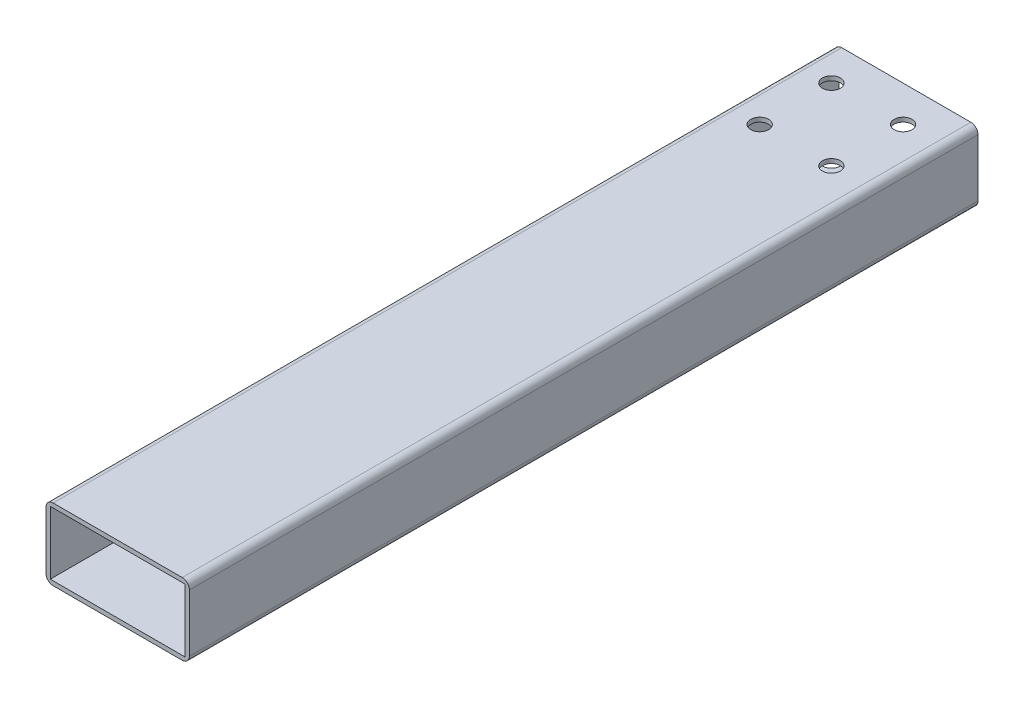
SolidWorks part; units mm, degrees
ref_plane "Front Plane" through (0, 0, 0) normal (0, 0, 1) x (1, 0, 0)
ref_plane "Top Plane" through (0, 0, 0) normal (0, 1, 0) x (1, 0, 0)
ref_plane "Right Plane" through (0, 0, 0) normal (1, 0, 0) x (0, 0, -1)
sketch "Sketch1" plane through (0, 0, 0) normal (0, 0, 1) x (1, 0, 0)
  line L1 (-24.2596, 11.4248) -> (26.5404, 11.4248)
  line L2 (-24.2596, 11.4248) -> (-24.2596, -13.9752)
  line L3 (-24.2596, -13.9752) -> (26.5404, -13.9752)
  line L4 (26.5404, 11.4248) -> (26.5404, -13.9752)
  line L5 (-22.7356, 9.9008) -> (25.0164, 9.9008)
  line L6 (-22.7356, 9.9008) -> (-22.7356, -12.4512)
  line L7 (-22.7356, -12.4512) -> (25.0164, -12.4512)
  line L8 (25.0164, 9.9008) -> (25.0164, -12.4512)
  dimension "D1" = 25.4
  dimension "D2" = 50.8
  dimension "D3" = 1.524
  dimension "D4" = 1.524
  dimension "D5" = 1.524
  dimension "D6" = 1.524
extrude "Boss-Extrude1" add sketch "Sketch1" along normal blind 279.4
fillet "Fillet1" radius 2.54 4 edges at (26.5404, -13.9752, 139.7) (-24.2596, -13.9752, 139.7) (-24.2596, 11.4248, 139.7) (26.5404, 11.4248, 139.7)
sketch "Sketch2" plane through (0, 11.4248, 0) normal (0, 1, 0) x (1, 0, 0)
  line L0 (24.0004, 0) -> (-21.7196, 0) construction
  line L1 (0, 0) -> (0, -59.7417) construction
  circle A0 centre (-12.7, -12.7) radius 3.175
  circle A1 centre (12.7, -12.7) radius 3.175
  circle A2 centre (-12.7, -38.1) radius 3.175
  circle A3 centre (12.7, -38.1) radius 3.175
  dimension "D1" = 6.35
  dimension "D2" = 6.35
  dimension "D3" = 6.35
  dimension "D4" = 6.35
  dimension "D5" = 25.4
  dimension "D6" = 25.4
  dimension "D7" = 12.7
  dimension "D8" = 12.7
extrude "Cut-Extrude1" cut sketch "Sketch2" against normal through all
